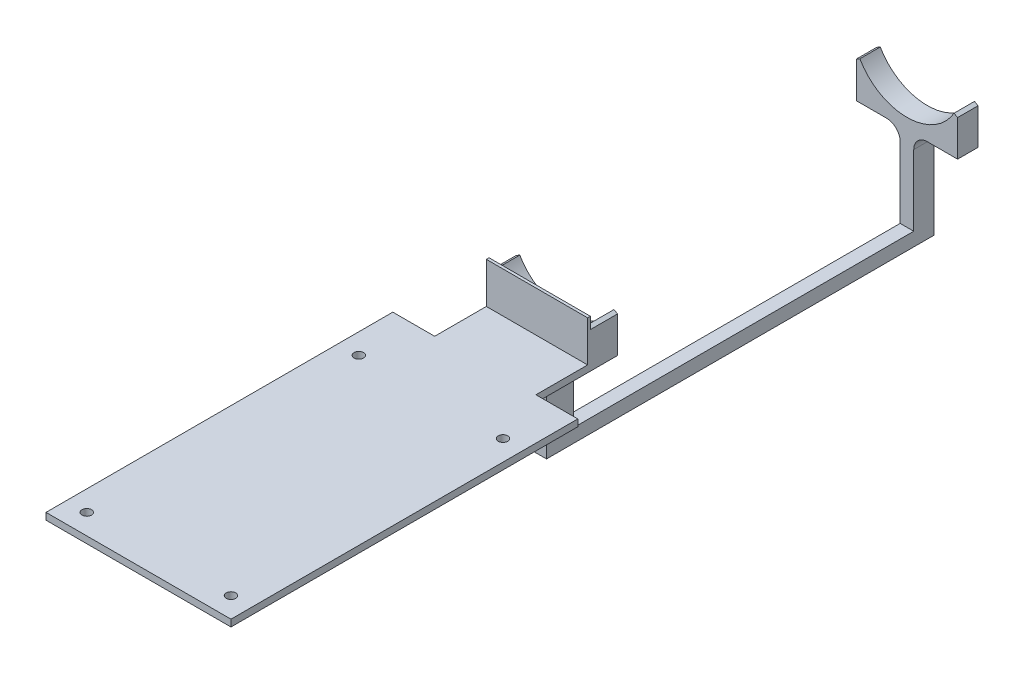
SolidWorks part; units mm, degrees
ref_plane "前视基准面" through (0, 0, 0) normal (0, 0, 1) x (1, 0, 0)
ref_plane "上视基准面" through (0, 0, 0) normal (0, 1, 0) x (1, 0, 0)
ref_plane "右视基准面" through (0, 0, 0) normal (1, 0, 0) x (0, 0, -1)
sketch "草图1" plane through (0, 0, 0) normal (0, 0, 1) x (1, 0, 0)
  line L0 (-34.641, -20) -> (-37.2391, -21.5)
  line L1 (34.641, -20) -> (37.2391, -21.5)
  line L2 (0, 48.2337) -> (0, -58.3658) construction
  arc A0 (-34.641, -20) -> (34.641, -20) centre (0, 0) ccw
  arc A1 (-37.2391, -21.5) -> (37.2391, -21.5) centre (0, 0) ccw
  dimension "D1" = 80
  dimension "D4" = 3
  dimension "D2" = 60
  dimension "D3" = 60
extrude "凸台-拉伸1" add sketch "草图1" along normal mid plane 20 from offset 130
extrude "凸台-拉伸2" add sketch "草图1<2>" against normal blind 15 from offset 130 offset against normal yes
sketch "草图1<2>" plane through (0, 0, 0) normal (0, 0, 1) x (1, 0, 0) same geometry as "草图1"
ref_plane "基准面1" through (0, -43, 0) normal (0, -1, 0) x (-1, 0, 0)
sketch "草图2" plane through (0, -43, 0) normal (0, -1, 0) x (-1, 0, 0)
  line L0 (0, -147.901) -> (0, -310.7547) construction
  line L1 (-37.2391, -180) -> (-68, -180)
  line L2 (-37.2391, -180) -> (-37.2391, -120)
  line L3 (-37.2391, -120) -> (37.2391, -120)
  line L4 (37.2391, -180) -> (37.2391, -120)
  line L5 (-35.3703, -285.8133) -> (37.2391, -120) construction
  line L6 (-37.2391, -120) -> (35.3703, -285.8133) construction
  line L8 (68, -434.9842) -> (-68, -434.9842)
  line L9 (68, -434.9842) -> (68, -180)
  line L10 (68, -180) -> (37.2391, -180)
  line L11 (-68, -434.9842) -> (-68, -180)
  line L12 (68, -434.9842) -> (-68, -180) construction
  line L13 (68, -180) -> (-68, -434.9842) construction
  circle A0 centre (-53, -220) radius 3.5
  circle A1 centre (-53, -420) radius 3.5
  circle A2 centre (53, -420) radius 3.5
  circle A3 centre (53, -220) radius 3.5
  point P0 (0, -205.0404)
  point P13 (0, -307.4921)
  dimension "D1" = 7
  dimension "D2" = 7
  dimension "D3" = 53
  dimension "D4" = 200
  dimension "D5" = 100
  dimension "D6" = 15
  dimension "D7" = 60
extrude "凸台-拉伸5" add sketch "草图2" along normal blind 5 separate body
sketch "草图5" plane through (0, 0, 120) normal (0, 0, -1) x (-1, 0, 0)
  line L0 (-37.2391, -21.5) -> (-37.2391, -48)
  line L2 (-37.2391, -48) -> (37.2391, -48)
  line L3 (37.2391, -48) -> (37.2391, -21.5)
  arc A0 (-37.2391, -21.5) -> (37.2391, -21.5) centre (0, 0) ccw construction
  arc A1 (-37.2391, -21.5) -> (37.2391, -21.5) centre (0, 0) ccw
  dimension "D1" = 48
extrude "凸台-拉伸11" add sketch "草图5" against normal blind 20
sketch "草图7" plane through (0, 0, -145) normal (0, 0, -1) x (-1, 0, 0)
  line L0 (37.2391, -21.5) -> (37.2391, -48)
  line L1 (37.2391, -48) -> (-37.2391, -48)
  line L2 (-37.2391, -48) -> (-37.2391, -21.5)
  arc A0 (-37.2391, -21.5) -> (37.2391, -21.5) centre (0, 0) ccw construction
  arc A1 (-37.2391, -21.5) -> (37.2391, -21.5) centre (0, 0) ccw
extrude "凸台-拉伸15" add sketch "草图7" against normal up to surface (15 mm away) up to face at (0, -31.125, -130)
sketch "草图8" plane through (0, 0, 0) normal (1, 0, 0) x (0, 0, -1)
  line L0 (-140, -43) -> (-140, -120)
  line L1 (-140, -120) -> (145, -120)
  line L2 (145, -43) -> (145, -120)
  line L3 (-140, -43) -> (-120, -43)
  line L4 (145, -21.5) -> (145, -48) construction
  line L5 (-120, -48) -> (-120, -43)
  line L6 (-120, -21.5) -> (-120, -48) construction
  line L7 (130, -48) -> (130, -43)
  line L8 (130, -21.5) -> (130, -48) construction
  line L9 (130, -48) -> (130, -110)
  line L10 (130, -110) -> (-120, -110)
  line L11 (-120, -110) -> (-120, -48)
  line L12 (130, -43) -> (145, -43)
  dimension "D1" = 120
  dimension "D2" = 10
extrude "凸台-拉伸16" add sketch "草图8" along normal mid plane 10
fillet "圆角1" radius 10 4 edges at (-5, -48, 130) (5, -48, 130) (-5, -48, -137.5) (5, -48, -137.5)
sketch "草图9" plane through (0, -43, 0) normal (0, 1, 0) x (1, 0, 0)
  line L0 (37.2391, -140) -> (37.2391, -180) construction
  line L1 (-37.2391, -140) -> (37.2391, -140)
  line L2 (-37.2391, -140) -> (-37.2391, -142)
  line L3 (-37.2391, -142) -> (37.2391, -142)
  line L4 (37.2391, -140) -> (37.2391, -142)
  dimension "D1" = 2
extrude "凸台-拉伸17" add sketch "草图9" along normal blind 30
